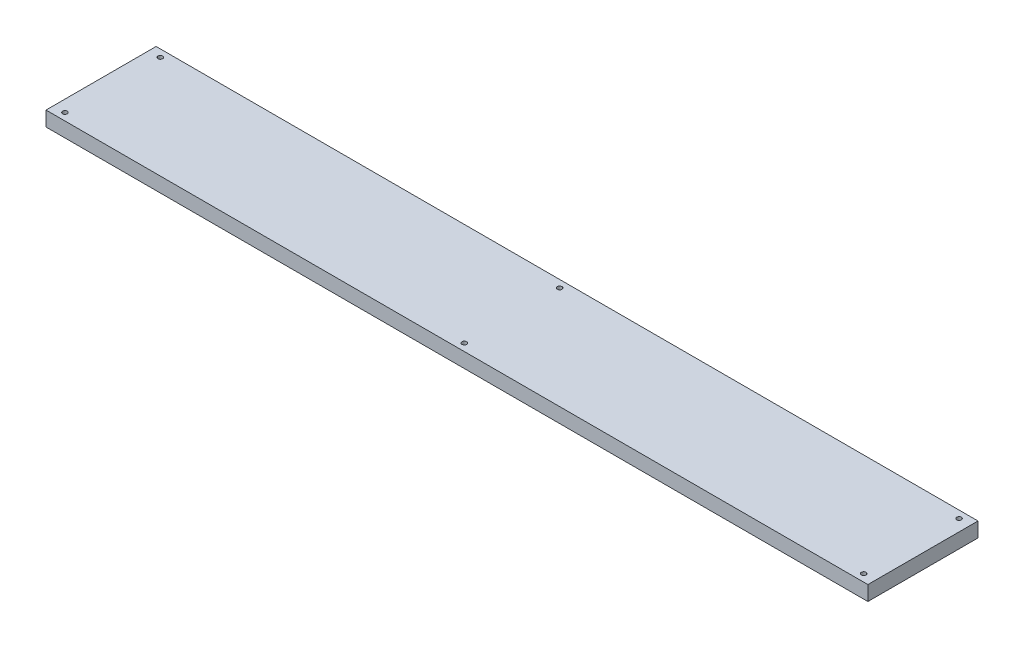
SolidWorks part; units mm, degrees
material "PE High Density Film"
ref_plane "Front Plane" through (0, 0, 0) normal (0, 0, 1) x (1, 0, 0)
ref_plane "Top Plane" through (0, 0, 0) normal (0, 1, 0) x (1, 0, 0)
ref_plane "Right Plane" through (0, 0, 0) normal (1, 0, 0) x (0, 0, -1)
sketch "Sketch1" plane through (0, 0, 0) normal (0, 1, 0) x (1, 0, 0)
  line L1 (0, 0) -> (709, 0)
  line L2 (0, 0) -> (0, 95)
  line L3 (0, 95) -> (709, 95)
  line L4 (709, 0) -> (709, 95)
  dimension "D1" = 95
  dimension "D2" = 709
extrude "Boss-Extrude1" add sketch "Sketch1" along normal blind 12.7
sketch "Sketch2" plane through (0, 0, 0) normal (0, -1, 0) x (1, 0, 0)
  line L0 (0, -6.35) -> (709, -6.35) construction
  line L1 (0, -95) -> (0, 0) construction
  line L2 (709, 0) -> (709, -95) construction
  line L3 (709, -88.65) -> (0, -88.65) construction
  line L5 (0, 0) -> (709, 0) construction
  line L6 (709, -95) -> (0, -95) construction
  circle A0 centre (10, -88.65) radius 2.0195
  circle A1 centre (354.5, -88.65) radius 2.0195
  circle A2 centre (699, -88.65) radius 2.0195
  circle A3 centre (699, -6.35) radius 2.0195
  circle A4 centre (354.5, -6.35) radius 2.0195
  circle A5 centre (10, -6.35) radius 2.0195
  dimension "D1" = 4.039
  dimension "D2" = 4.039
  dimension "D3" = 4.039
  dimension "D4" = 4.039
  dimension "D5" = 4.039
  dimension "D6" = 4.039
  dimension "D7" = 344.5
  dimension "D8" = 344.5
  dimension "D9" = 344.5
  dimension "D10" = 344.5
  dimension "D12" = 6.35
  dimension "D13" = 6.35
extrude "Cut-Extrude1" cut sketch "Sketch2" against normal through all
